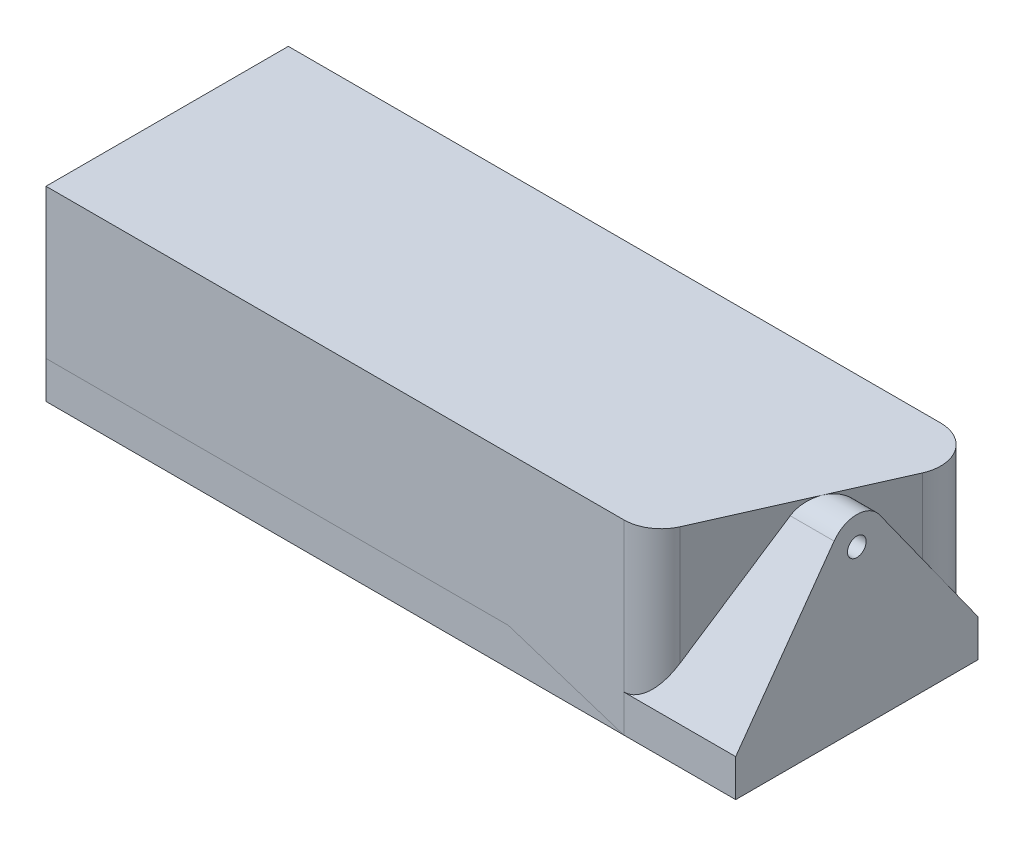
SolidWorks part; units mm, degrees
ref_plane "Front Plane" through (0, 0, 0) normal (0, 0, 1) x (1, 0, 0)
ref_plane "Top Plane" through (0, 0, 0) normal (0, 1, 0) x (1, 0, 0)
ref_plane "Right Plane" through (0, 0, 0) normal (1, 0, 0) x (0, 0, -1)
sketch "Sketch1" plane through (0, 0, 0) normal (0, 1, 0) x (1, 0, 0)
  line L0 (0, -10.3187) -> (0, 10.3187)
  line L1 (0, 10.3187) -> (55.5625, 10.3188)
  line L2 (58.4639, 5.8543) -> (52.1139, -8.4332)
  line L3 (49.2125, -10.3187) -> (0, -10.3187)
  arc A0 (55.5625, 10.3188) -> (58.4639, 5.8543) centre (55.5625, 7.1437) cw
  arc A1 (52.1139, -8.4332) -> (49.2125, -10.3187) centre (49.2125, -7.1437) cw
  point P4 (0, 0)
  point P11 (46.0375, 10.3187)
  dimension "D4" = 3.175
  dimension "D1" = 20.6375
  dimension "D2" = 46.0375
  dimension "D3" = 9.525
  dimension "D5" = 6.35
sketch "Sketch2" plane through (0, 0, 0) normal (0, 0, 1) x (1, 0, 0)
  line L0 (0, 0) -> (0, 3.175)
  line L1 (0, 3.175) -> (1.5875, 3.175)
  line L2 (1.5875, 3.175) -> (1.5875, 15.875)
  line L3 (1.5875, 15.875) -> (3.9688, 15.875)
  line L4 (3.9688, 15.875) -> (3.9688, 3.175)
  line L5 (3.9688, 3.175) -> (7.1438, 3.175)
  line L6 (7.1438, 3.175) -> (7.1438, 15.875)
  line L7 (7.1438, 15.875) -> (9.525, 15.875)
  line L8 (9.525, 15.875) -> (9.525, 3.175)
  line L9 (9.525, 3.175) -> (28.575, 3.175)
  line L10 (28.575, 3.175) -> (28.575, 0)
  line L11 (28.575, 0) -> (0, 0)
  dimension "D1" = 3.175
  dimension "D2" = 1.5875
  dimension "D3" = 12.7
  dimension "D4" = 2.3813
  dimension "D5" = 3.175
  dimension "D6" = 28.575
sketch "Sketch3" plane through (0, 0, 0) normal (1, 0, 0) x (0, 0, -1)
  line L0 (10.3187, 0) -> (-10.3187, 0)
  line L2 (-10.3187, 0) -> (-10.3187, 3.175)
  line L3 (-10.3187, 3.175) -> (-1.936, 14.8802)
  line L4 (1.936, 14.8802) -> (10.3187, 3.175)
  line L5 (10.3187, 3.175) -> (10.3187, 0)
  arc A0 (-1.936, 14.8802) -> (1.936, 14.8802) centre (0, 13.4937) cw
  circle A1 centre (0, 13.4937) radius 0.7937
  point P4 (0, 0)
  dimension "D4" = 2.3813
  dimension "D1" = 20.6375
  dimension "D5" = 1.5875
  dimension "D2" = 3.175
  dimension "D3" = 10.3187
extrude "Boss-Extrude1" add sketch "Sketch1" along normal blind 15.875
extrude "Boss-Extrude2" add sketch "Sketch2" along normal blind 10.3187 and the other way blind 10.3187 separate body
extrude "Boss-Extrude3" add sketch "Sketch3" along normal blind 58.7375 separate body
equation "\"D6@Sketch2\"= \"D1@Boss-Extrude1\" + \"D3@Sketch1\" + \"D4@Sketch1\""
equation "\"D1@Sketch3\" = \"D1@Sketch1\""
equation "\"D2@Sketch3\"= \"D1@Sketch2\""
equation "\"D3@Sketch2\"= \"D3@Sketch3\" + \"D4@Sketch3\""
equation "\"D1@Boss-Extrude1\"= \"D1@Sketch2\" + \"D3@Sketch3\" + \"D4@Sketch3\""
equation "\"D1@Boss-Extrude2\" = \"D1@Sketch1\" / 2"
equation "\"D2@Boss-Extrude2\"= \"D1@Boss-Extrude2\""
equation "\"D1@Boss-Extrude3\"= \"D2@Sketch1\" + \"D3@Sketch1\" + \"D4@Sketch1\""
